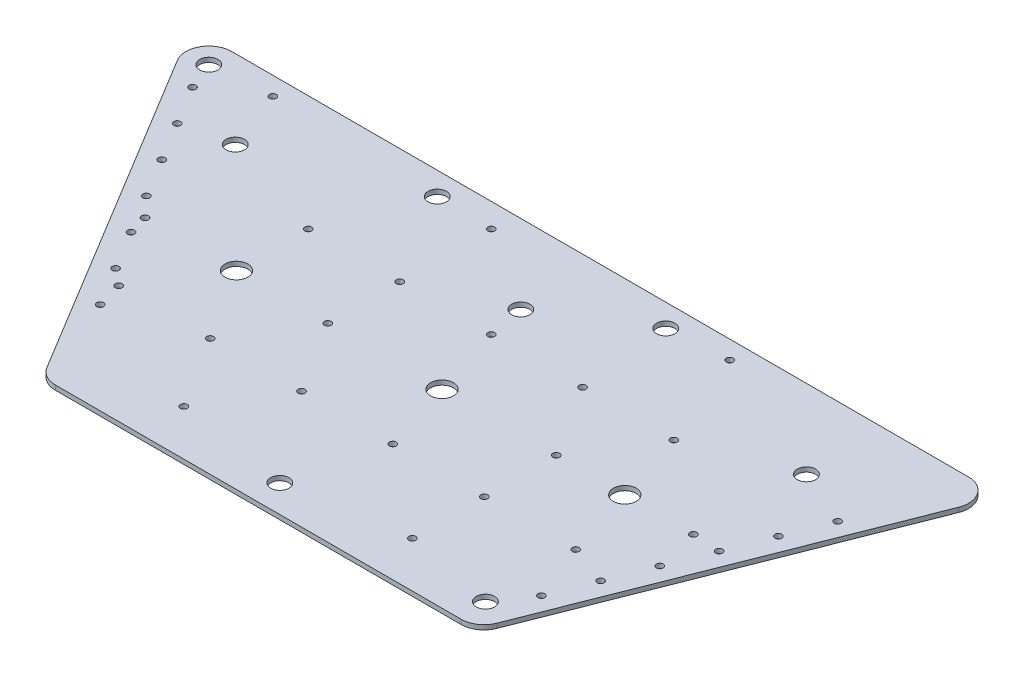
SolidWorks part; units mm, degrees
ref_plane "Front Plane" through (0, 0, 0) normal (0, 0, 1) x (1, 0, 0)
ref_plane "Top Plane" through (0, 0, 0) normal (0, 1, 0) x (1, 0, 0)
ref_plane "Right Plane" through (0, 0, 0) normal (1, 0, 0) x (0, 0, -1)
sketch "Sketch2" plane through (0, 0, 0) normal (0, 1, 0) x (1, 0, 0)
  line L0 (0, 0) -> (65, 165)
  line L1 (65, 165) -> (-290, 165)
  line L2 (-290, 165) -> (-190, 0)
  line L3 (-55, 0) -> (55, 0) construction
  line L4 (-190, 0) -> (0, 0)
  line L5 (0, -55) -> (0, 55) construction
  dimension "D1" = 355
  dimension "D2" = 190
  dimension "D3" = 165
  dimension "D4" = 65
extrude "Boss-Extrude1" add sketch "Sketch2" along normal blind 2
fillet "Fillet1" radius 10 4 edges at (-190, 1, 0) (-290, 1, -165) (65, 1, -165) (0, 1, 0)
sketch "Sketch3" plane through (0, 2, 0) normal (0, 1, 0) x (1, 0, 0)
  line L1 (50.3126, 165) -> (-272.2462, 165) construction
  line L2 (-280.7982, 149.817) -> (-192.9194, 4.817) construction
  line L3 (2.4955, 6.3348) -> (59.6167, 151.3348) construction
  line L5 (-1.1, 0) -> (1.1, 0) construction
  line L6 (-261.9073, 134.0821) -> (-194.8085, 23.369) construction
  line L7 (-4.3733, 10.7251) -> (45.6685, 137.7543) construction
  circle A0 centre (-272.2462, 155) radius 10 construction
  circle A1 centre (-228.1703, 83) radius 1.5
  circle A2 centre (-246.2462, 157) radius 1.5
  circle A3 centre (-46.2462, 157) radius 1.5
  circle A4 centre (11.8297, 83) radius 1.5
  circle A42 centre (-272.2462, 155) radius 4
  circle A43 centre (-172.2462, 155) radius 4
  circle A44 centre (13.8297, 130.5) radius 4
  circle A45 centre (-236.1703, 130.5) radius 4
  circle A46 centre (-111.1703, 130.5) radius 4
  circle A47 centre (-18.1703, 83) radius 5
  circle A48 centre (-188.1703, 83) radius 5
  circle A49 centre (-98.1703, 83) radius 5
  circle A50 centre (-205.05, 40.2675) radius 1.5
  circle A51 centre (-208.1703, 51.5) radius 1.5
  circle A52 centre (-225.7821, 74.4754) radius 1.5
  circle A53 centre (-236.1481, 91.5794) radius 1.5
  circle A54 centre (-246.5141, 108.6833) radius 1.5
  circle A55 centre (-256.8802, 125.7873) radius 1.5
  circle A56 centre (-267.2462, 142.8912) radius 1.5
  circle A57 centre (1.8297, 26.4713) radius 1.5
  circle A58 centre (9.1602, 45.0795) radius 1.5
  circle A59 centre (16.4907, 63.6876) radius 1.5
  circle A60 centre (23.8212, 82.2958) radius 1.5
  circle A61 centre (31.1517, 100.904) radius 1.5
  circle A62 centre (38.4822, 119.5121) radius 1.5
  circle A63 centre (-72.2462, 155) radius 4
  circle A64 centre (-148.1703, 154.5) radius 1.5
  circle A65 centre (-188.1703, 114.5) radius 1.5
  circle A66 centre (-148.1703, 114.5) radius 1.5
  circle A67 centre (-108.1703, 114.5) radius 1.5
  circle A68 centre (-68.1703, 114.5) radius 1.5
  circle A69 centre (-28.1703, 114.5) radius 1.5
  circle A70 centre (-148.1703, 83) radius 1.5
  circle A71 centre (-215.416, 57.3715) radius 1.5
  circle A72 centre (-168.1703, 51.5) radius 1.5
  circle A73 centre (-8.1703, 51.5) radius 1.5
  circle A74 centre (-128.1703, 51.5) radius 1.5
  circle A75 centre (-88.1703, 51.5) radius 1.5
  circle A76 centre (-48.1703, 83) radius 1.5
  circle A77 centre (-48.1703, 51.5) radius 1.5
  circle A78 centre (-8.1703, 12) radius 4
  circle A79 centre (-148.1703, 20) radius 1.5
  circle A80 centre (-98.1703, 12) radius 4
  circle A81 centre (-48.1703, 20) radius 1.5
  dimension "D1" = 3
  dimension "D2" = 8
  dimension "D3" = 20
  dimension "D4" = 20
  dimension "D6" = 20
  dimension "D7" = 20
  dimension "D8" = 20
  dimension "D9" = 8
  dimension "D10" = 5
  dimension "D11" = 20
  dimension "D12" = 12
  dimension "D13" = 31.5
  dimension "D14" = 31.5
  dimension "D15" = 31.5
  dimension "D16" = 40
  dimension "D17" = 40
  dimension "D18" = 40
  dimension "D19" = 40
  dimension "D20" = 40
  dimension "D21" = 40
  dimension "D22" = 12
  dimension "D24" = 40
  dimension "D25" = 90
  dimension "D26" = 80
  dimension "D27" = 50
  dimension "D28" = 10
  dimension "D29" = 40
  dimension "D30" = 40
  dimension "D31" = 40
  dimension "D32" = 40
  dimension "D33" = 3
  dimension "D34" = 16
  dimension "D35" = 125
  dimension "D37" = 8
  dimension "D38" = 10
  dimension "D39" = 20
  dimension "D40" = 20
  dimension "D41" = 20
  dimension "D42" = 20
  dimension "D43" = 20
  dimension "D44" = 100
  dimension "D45" = 100
  dimension "D46" = 40
  dimension "D47" = 30
  dimension "D48" = 8
  dimension "D5" = 20
  dimension "D23" = 90
  dimension "D36" = 125
  dimension "D49" = 26
  dimension "D50" = 200
extrude "Cut-Extrude1" cut sketch "Sketch3" against normal blind 2
